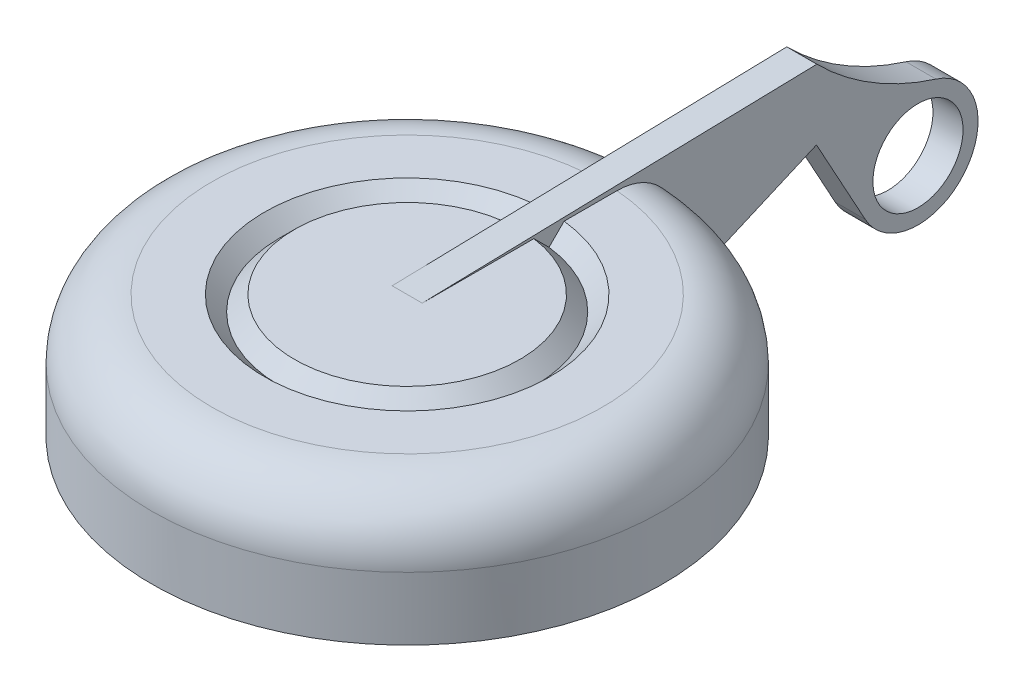
SolidWorks part; units mm, degrees
ref_plane "Front Plane" through (0, 0, 0) normal (0, 0, 1) x (1, 0, 0)
ref_plane "Top Plane" through (0, 0, 0) normal (0, 1, 0) x (1, 0, 0)
ref_plane "Right Plane" through (0, 0, 0) normal (1, 0, 0) x (0, 0, -1)
sketch "Sketch4" plane through (0, 0, 0) normal (1, 0, 0) x (0, 0, -1)
  line L0 (0, 0) -> (-3.75, 0)
  line L1 (-3.75, 0) -> (-4.25, -0.5)
  line L2 (-4.25, -0.5) -> (-4.75, 0)
  line L3 (-4.75, 0) -> (-8.5, 0)
  line L4 (-8.5, 0) -> (-8.5, -4)
  line L5 (-8.5, -4) -> (0, -4)
  line L6 (0, 0) -> (0, -4)
  line L7 (-8.5, -0.5) -> (0, -0.5) construction
  line L8 (0, 1.8905) -> (0, -6.6755) construction
  point P3 (-4.25, -0.5)
  dimension "D1" = 8.5
  dimension "D2" = 0.5
  dimension "D3" = 4
revolve "Revolve1" add sketch "Sketch4" angle 360 about L8
fillet "Fillet1" radius 2 1 edges at (0, 0, 8.5)
sketch "Sketch5" plane through (0, -4, 0) normal (0, -1, 0) x (1, 0, 0)
  circle A0 centre (0, 0) radius 8.5
  circle A1 centre (0, 0) radius 7
  dimension "D1" = 14
extrude "Boss-Extrude1" add sketch "Sketch5" along normal blind 0.1 separate body
sketch "Sketch6" plane through (0, 0, 0) normal (1, 0, 0) x (0, 0, -1)
  line L0 (0, 0) -> (13.1329, 0.32)
  line L1 (8.5, -4) -> (13.1218, -1.9998)
  line L2 (8.5, -4) -> (8.5, -2) construction
  line L3 (8.5, -4) -> (-8.5, -4) construction
  line L4 (13.1218, -1.9998) -> (14.7464, -4.9618)
  line L5 (0, 0) -> (0, -0.9077)
  line L6 (0, -0.9077) -> (7.1744, -0.9077)
  line L7 (7.1744, -0.9077) -> (8.5, -4)
  circle A0 centre (16.5, -4) radius 1.5
  circle A1 centre (16.5, -4) radius 2
  arc A2 (13.1329, 0.32) -> (17.0986, -2.0917) centre (19.992, 7.1325) ccw
  dimension "D1" = 3
  dimension "D2" = 4
  dimension "D3" = 16.5
extrude "Boss-Extrude2" add sketch "Sketch6" along normal blind 0.5 and the other way blind 0.5 contours A2 L0 L5 L6 L7 L1 L4 A1 | A1 A0 region at (0, -1.2698, -9.4758) region at (0, -2.8497, -18.0664)
